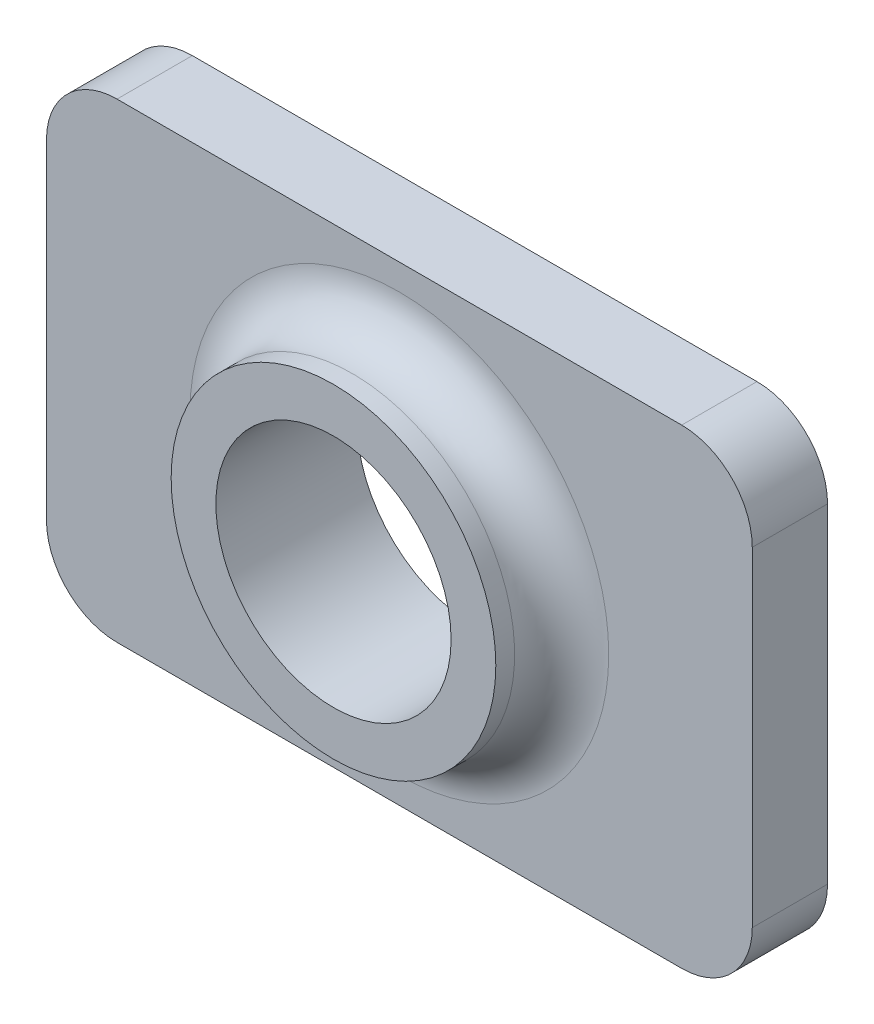
SolidWorks part; units mm, degrees
ref_plane "Front Plane" through (0, 0, 0) normal (0, 0, 1) x (1, 0, 0)
ref_plane "Top Plane" through (0, 0, 0) normal (0, 1, 0) x (1, 0, 0)
ref_plane "Right Plane" through (0, 0, 0) normal (1, 0, 0) x (0, 0, -1)
sketch "Sketch1" plane through (0, 0, 0) normal (0, 0, 1) x (1, 0, 0)
  line L1 (0, 0) -> (15, 0)
  line L2 (0, 0) -> (0, 10)
  line L3 (0, 10) -> (15, 10)
  line L4 (15, 0) -> (15, 10)
  dimension "D1" = 15
  dimension "D2" = 10
extrude "Boss-Extrude1" add sketch "Sketch1" along normal blind 1.6
fillet "Fillet1" radius 1.5 4 edges at (15, 0, 0.8) (0, 0, 0.8) (0, 10, 0.8) (15, 10, 0.8)
sketch "Sketch2" plane through (0, 0, 1.6) normal (0, 0, 1) x (1, 0, 0)
  line L0 (0, 5) -> (7.5, 5) construction
  line L1 (0, 8.5) -> (0, 1.5) construction
  line L2 (7.5, 5) -> (7.5, 10) construction
  line L3 (13.5, 10) -> (1.5, 10) construction
  circle A0 centre (7.5, 5) radius 3.45
  circle A1 centre (7.5, 5) radius 2.5
extrude "Boss-Extrude2" add sketch "Sketch2" along normal blind 1.4 contours A0
extrude "Cut-Extrude1" cut sketch "Sketch2<3>" against normal blind 1.6 and the other way blind 1.4 contours A1
sketch "Sketch2<3>" plane through (0, 0, 1.6) normal (0, 0, 1) x (1, 0, 0) same geometry as "Sketch2"
ref_plane "Plane1" through (0, 0, 3.5) normal (0, 0, 1) x (1, 0, 0)
fillet "Fillet2" radius 1 1 edges at (4.05, 5, 1.6)
